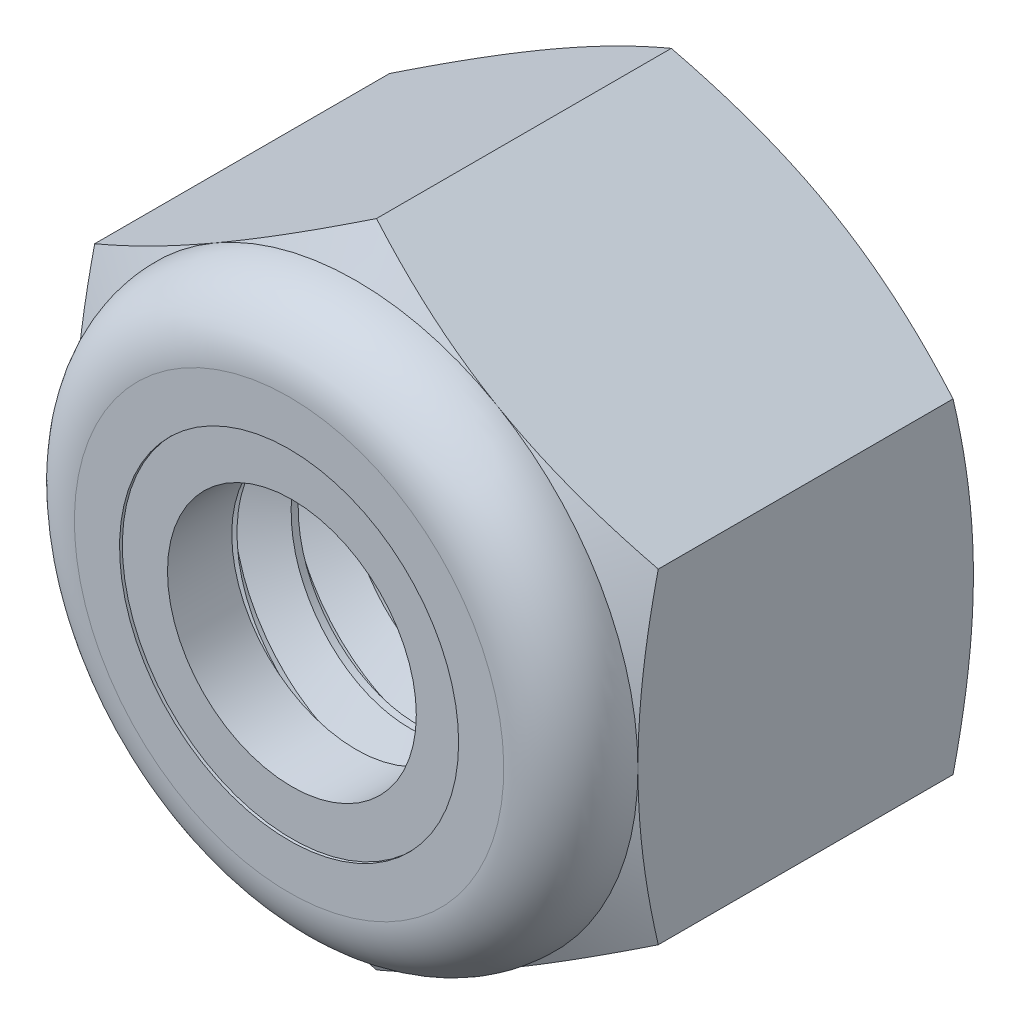
SolidWorks part; units mm, degrees
ref_plane "Front Plane" through (0, 0, 0) normal (0, 0, 1) x (1, 0, 0)
ref_plane "Top Plane" through (0, 0, 0) normal (0, 1, 0) x (1, 0, 0)
ref_plane "Right Plane" through (0, 0, 0) normal (1, 0, 0) x (0, 0, -1)
sketch "Sketch1" plane through (0, 0, 0) normal (0, 0, 1) x (1, 0, 0)
  line L1 (0, 4.0415) -> (-3.5, 2.0207)
  line L2 (-3.5, 2.0207) -> (-3.5, -2.0207)
  line L3 (-3.5, -2.0207) -> (0, -4.0415)
  line L4 (0, -4.0415) -> (3.5, -2.0207)
  line L5 (3.5, -2.0207) -> (3.5, 2.0207)
  line L6 (3.5, 2.0207) -> (0, 4.0415)
  circle A0 centre (0, 0) radius 3.5 construction
  circle A1 centre (0, 0) radius 2
  point P10 (0, -2)
  point P11 (0, 2)
  point P12 (0, 3.5)
  dimension "Thread Size" = 4
  dimension "Width" = 7
sketch "Sketch2" plane through (0, 0, 0) normal (1, 0, 0) x (0, 0, -1)
  line L0 (2.5, 0) -> (-2.5, 0) construction
  line L1 (-2.5, 2) -> (2.5, 2) construction
  line L2 (-2.465, -2.106) -> (-3.77, -2.106) construction
  line L3 (-3.1563, 2.0758) -> (-2.4563, 2.0758) construction
  line L4 (-2.4563, 2.0758) -> (-2.8063, 1.4696) construction
  line L5 (-2.8063, 1.4696) -> (-3.1563, 2.0758) construction
  line L6 (-3.1125, 2) -> (-2.5, 2) construction
  line L7 (-2.85, 1.5453) -> (-2.7625, 1.5453) construction
  line L8 (-2.8063, 1.5453) -> (-2.8063, 1.4696) construction
  line L9 (-2.8063, 2) -> (-2.8063, 2.0758) construction
  line L10 (-2.4781, 2.0379) -> (-3.1344, 2.0379)
  line L11 (-3.1344, 2.0379) -> (-2.85, 1.5453)
  line L12 (-2.85, 1.5453) -> (-2.7625, 1.5453)
  line L13 (-2.7625, 1.5453) -> (-2.4781, 2.0379)
  line L14 (2.5, 0) -> (3.77, 0)
  line L15 (3.77, 0) -> (3.77, 5.3115)
  line L16 (0, 5.3115) -> (0, 4.0415) construction
  line L17 (0, 4.0415) -> (0, 2.0207) construction
  line L18 (2.5, 3.5) -> (-1.6667, 3.5) construction
  line L19 (-2.85, -1.5453) -> (-2.7625, -1.5453) construction
  line L20 (2.5, 3.5) -> (2.5, 0)
  line L21 (2.2475, 4.0415) -> (-1.4142, 4.0415)
  line L22 (2.5, 3.5) -> (2.2475, 4.0415)
  line L23 (-2.5, 0) -> (-2.5, 2.6667) construction
  line L24 (-1.6667, 3.5) -> (-1.4142, 4.0415)
  line L25 (3.77, 5.3115) -> (-3.77, 5.3115)
  line L26 (-2.5, 2.6667) -> (-3.77, 2.6667)
  line L27 (-3.77, 2.6667) -> (-3.77, 5.3115)
  line L28 (-2.465, 2.6667) -> (-2.465, 1.5453) construction
  line L29 (-2.465, 2.106) -> (-3.77, 2.106)
  line L30 (-3.77, 2.106) -> (-3.77, 0)
  line L31 (-3.77, 0) -> (-1.6667, 0)
  line L32 (-1.6667, 0) -> (-1.6667, 3.465)
  line L33 (-2.465, 2.106) -> (-2.465, 2.6667)
  arc A0 (-1.6667, 3.5) -> (-2.5, 2.6667) centre (-1.6667, 2.6667) ccw
  arc A1 (-1.6667, 3.465) -> (-2.465, 2.6667) centre (-1.6667, 2.6667) ccw
  point P4 (0, 0)
  point P18 (-2.8063, 2.0379)
  point P22 (-2.8063, 2.0379)
  point P33 (0, 4.0415)
  point P48 (-3.77, -2.106)
  point P51 (-2.85, -1.5453)
  dimension "Height" = 5
  dimension "Pitch" = 0.7
  dimension "D1" = 0.0875
  dimension "D2" = 1.27
  dimension "D3" = 25
  dimension "D4" = 0.8333
  dimension "D5" = 25
  dimension "D6" = 0.035
sketch "Sketch3" plane through (0, 0, 0) normal (0, 0, 1) x (1, 0, 0)
  line L0 (0, -4.0415) -> (3.5, -2.0207) construction
  line L1 (3.5, -2.0207) -> (3.5, 2.0207) construction
  line L2 (3.5, 2.0207) -> (0, 4.0415) construction
  line L3 (0, 4.0415) -> (-3.5, 2.0207) construction
  line L4 (-3.5, 2.0207) -> (-3.5, -2.0207) construction
  line L5 (-3.5, -2.0207) -> (0, -4.0415) construction
  line L6 (0, -4.0415) -> (3.5, -2.0207)
  line L7 (3.5, -2.0207) -> (3.5, 2.0207)
  line L8 (3.5, 2.0207) -> (0, 4.0415)
  line L9 (0, 4.0415) -> (-3.5, 2.0207)
  line L10 (-3.5, 2.0207) -> (-3.5, -2.0207)
  line L11 (-3.5, -2.0207) -> (0, -4.0415)
  circle A0 centre (0, 0) radius 2 construction
  circle A1 centre (0, 0) radius 2
extrude "Boss-Extrude1" add sketch "Sketch3" along normal mid plane 5
sketch "Sketch4" plane through (0, 0, 0) normal (1, 0, 0) x (0, 0, -1)
  line L0 (3.77, 5.3115) -> (-3.77, 5.3115) construction
  line L1 (-3.77, 2.6667) -> (-3.77, 5.3115) construction
  line L2 (-2.5, 2.6667) -> (-3.77, 2.6667) construction
  line L3 (-1.6667, 3.5) -> (-1.4142, 4.0415) construction
  line L4 (2.2475, 4.0415) -> (-1.4142, 4.0415) construction
  line L5 (2.5, 3.5) -> (2.2475, 4.0415) construction
  line L6 (2.5, 3.5) -> (2.5, 0) construction
  line L7 (2.5, 0) -> (3.77, 0) construction
  line L8 (3.77, 0) -> (3.77, 5.3115) construction
  line L9 (-3.77, 2.106) -> (-3.77, 0) construction
  line L10 (-3.77, 0) -> (-1.6667, 0) construction
  line L11 (-1.6667, 0) -> (-1.6667, 3.465) construction
  line L12 (-2.465, 2.106) -> (-2.465, 2.6667) construction
  line L13 (-2.465, 2.106) -> (-3.77, 2.106) construction
  line L14 (3.77, 5.3115) -> (-3.77, 5.3115)
  line L15 (-3.77, 2.6667) -> (-3.77, 5.3115)
  line L16 (-2.5, 2.6667) -> (-3.77, 2.6667)
  line L17 (-1.6667, 3.5) -> (-1.4142, 4.0415)
  line L18 (2.2475, 4.0415) -> (-1.4142, 4.0415)
  line L19 (2.5, 3.5) -> (2.2475, 4.0415)
  line L20 (2.5, 3.5) -> (2.5, 0)
  line L21 (2.5, 0) -> (3.77, 0)
  line L22 (3.77, 0) -> (3.77, 5.3115)
  line L23 (-3.77, 2.106) -> (-3.77, 0)
  line L24 (-3.77, 0) -> (-1.6667, 0)
  line L25 (-1.6667, 0) -> (-1.6667, 3.465)
  line L26 (-2.465, 2.106) -> (-2.465, 2.6667)
  line L27 (-2.465, 2.106) -> (-3.77, 2.106)
  arc A0 (-1.6667, 3.5) -> (-2.5, 2.6667) centre (-1.6667, 2.6667) ccw construction
  arc A1 (-1.6667, 3.465) -> (-2.465, 2.6667) centre (-1.6667, 2.6667) ccw construction
  arc A2 (-1.6667, 3.5) -> (-2.5, 2.6667) centre (-1.6667, 2.6667) ccw
  arc A3 (-1.6667, 3.465) -> (-2.465, 2.6667) centre (-1.6667, 2.6667) ccw
revolve "Cut-Revolve1" cut sketch "Sketch4" angle 360 about L0
sketch "Sketch5" plane through (0, 0, 0) normal (1, 0, 0) x (0, 0, -1)
  line L0 (-2.465, 2.6667) -> (-2.465, 1.5453) construction
  line L1 (-1.6667, 0) -> (-1.6667, 3.465) construction
  line L2 (-2.465, 2.6667) -> (-2.465, 1.5453)
  line L3 (-1.6667, 1.5453) -> (-1.6667, 3.465)
  line L4 (-2.465, 1.5453) -> (-1.6667, 1.5453)
  arc A0 (-1.6667, 3.465) -> (-2.465, 2.6667) centre (-1.6667, 2.6667) ccw construction
  arc A1 (-1.6667, 3.465) -> (-2.465, 2.6667) centre (-1.6667, 2.6667) ccw
revolve "Revolve1" add sketch "Sketch5" angle 360 about L0
sketch "Sketch6" plane through (0, 0, 2.5) normal (0, 0, 1) x (1, 0, 0)
  circle A0 centre (0, 0) radius 2 construction
  circle A1 centre (0, 0) radius 2
curve "Helix/Spiral1" pitch 0.7 height 5.7 radius 2 centre (0, 0, 2.5) axis (0, 0, -1) start towards (0, 1, 0)
sketch "Sketch7" plane through (0, 0, 0) normal (1, 0, 0) x (0, 0, -1)
  line L0 (-3.1344, 2.0379) -> (-2.85, 1.5453) construction
  line L1 (-2.85, 1.5453) -> (-2.7625, 1.5453) construction
  line L2 (-2.7625, 1.5453) -> (-2.4781, 2.0379) construction
  line L3 (-2.4781, 2.0379) -> (-3.1344, 2.0379) construction
  line L4 (-3.1344, 2.0379) -> (-2.85, 1.5453)
  line L5 (-2.85, 1.5453) -> (-2.7625, 1.5453)
  line L6 (-2.7625, 1.5453) -> (-2.4781, 2.0379)
  line L7 (-2.4781, 2.0379) -> (-3.1344, 2.0379)
sweep "Sweep1" add profiles "Sketch7" path "Helix/Spiral1"
sketch "Sketch8" plane through (0, 0, -2.5) normal (0, 0, -1) x (-1, 0, 0)
  circle A2 centre (0, 0) radius 2.0379
  point P2 (0, 2.0379)
extrude "Cut-Extrude1" cut sketch "Sketch8" along normal through all and the other way through all draft 60
sketch "Sketch9" plane through (0, 0, 1.6667) normal (0, 0, 1) x (1, 0, 0)
  circle A2 centre (0, 0) radius 2.0379
  circle A3 centre (0, 0) radius 1.5453 construction
  point P2 (0, 2.0379)
  point P4 (0, 1.5453)
extrude "Cut-Extrude2" cut sketch "Sketch9" along normal through all and the other way through all draft 60
equation "\"D1@Sketch2\" = \"Pitch@Sketch2\" / 8"
equation "\"D4@Sketch2\"=\"Height@Sketch2\"/6"
equation "\"D1@Boss-Extrude1\"=\"Height@Sketch2\""
equation "\"D3@Helix/Spiral1\"=\"Height@Sketch2\"+\"Pitch@Sketch2\""
equation "\"D4@Helix/Spiral1\"=\"Pitch@Sketch2\""
equation "\"D6@Sketch2\"=\"Pitch@Sketch2\"*0.05"
